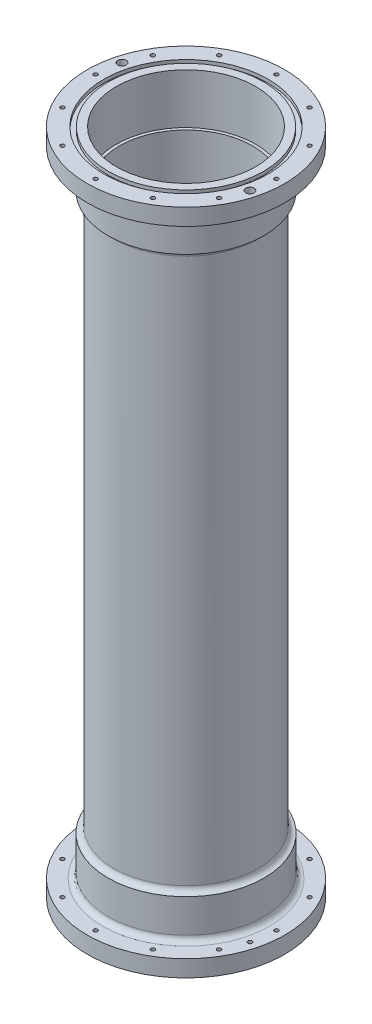
SolidWorks part; units mm, degrees
material "7075-T6 (SN)"
ref_plane "Front Plane" through (0, 0, 0) normal (0, 0, 1) x (1, 0, 0)
ref_plane "Top Plane" through (0, 0, 0) normal (0, 1, 0) x (1, 0, 0)
ref_plane "Right Plane" through (0, 0, 0) normal (1, 0, 0) x (0, 0, -1)
sketch "Sketch2" plane through (0, 0, 0) normal (0, 1, 0) x (1, 0, 0)
  circle A0 centre (0, 0) radius 38.1
  circle A1 centre (0, 0) radius 41.275
  dimension "D1" = 82.55
  dimension "D2" = 76.2
extrude "Base Cylinder" add sketch "Sketch2" along normal blind 381
sketch "Sketch3" plane through (0, 0, 0) normal (0, -1, 0) x (1, 0, 0)
  circle A0 centre (0, 0) radius 38.1
  circle A1 centre (0, 0) radius 56.3562
  dimension "D1" = 112.7125
extrude "Aft Flange" add sketch "Sketch3" against normal blind 9.525
sketch "Sketch34" plane through (0, 0, 0) normal (0, -1, 0) x (1, 0, 0)
  circle A0 centre (0, 0) radius 39.75
  dimension "D1" = 79.5
extrude "TemperatureInsert" cut sketch "Sketch34" against normal blind 28.575
sketch "Sketch6" plane through (0, 0, 0) normal (0, -1, 0) x (1, 0, 0)
  circle A0 centre (0, 0) radius 46.9011
  circle A1 centre (0, 0) radius 44.2849
  dimension "D1" = 93.8022
  dimension "D2" = 88.5698
extrude "Aft O-Ring" cut sketch "Sketch6" against normal blind 1.9812
sketch "Sketch33" plane through (0, 9.525, 0) normal (0, 1, 0) x (1, 0, 0)
  circle A0 centre (0, 0) radius 41.275
  circle A1 centre (0, 0) radius 44.45
  dimension "D1" = 82.55
  dimension "D2" = 88.9
extrude "CriticalBoss" add sketch "Sketch33" along normal blind 22.225
fillet "Fillet1" radius 3.175 2 edges at (0, 9.525, -44.45) (0, 31.75, 41.275)
sketch "Sketch For Bolt Holes" plane through (0, 0, 0) normal (0, -1, 0) x (1, 0, 0)
  circle A0 centre (-51.6255, 0) radius 1.5875
  circle A1 centre (-44.709, 25.8128) radius 1.5875
  circle A2 centre (-25.8128, 44.709) radius 1.5875
  circle A3 centre (0, 51.6255) radius 1.5875
  circle A4 centre (25.8127, 44.709) radius 1.5875
  circle A5 centre (44.709, 25.8128) radius 1.5875
  circle A6 centre (51.6255, 0) radius 1.5875
  circle A7 centre (44.709, -25.8127) radius 1.5875
  circle A8 centre (25.8128, -44.709) radius 1.5875
  circle A9 centre (0, -51.6255) radius 1.5875
  circle A10 centre (-25.8127, -44.709) radius 1.5875
  circle A11 centre (-44.709, -25.8128) radius 1.5875
  point P36 (0, 0)
  dimension "D2" = 3.175
  dimension "D1" = 51.6255
  dimension "D3" = 12
hole_wizard "Bolt Circle" positions "Sketch8" profile "Sketch9" hole size "#4-40" standard "ANSI Inch" end condition up to next
sketch "Sketch8" plane through (0, 0, 0) normal (0, -1, 0) x (-1, 0, 0)
  point P0 (-25.8127, -44.709)
  point P3 (-44.709, -25.8128)
  point P6 (-51.6255, 0)
  point P9 (-44.709, 25.8127)
  point P12 (-25.8128, 44.709)
  point P15 (0, 51.6255)
  point P18 (25.8127, 44.709)
  point P21 (44.709, 25.8128)
  point P24 (51.6255, 0)
  point P27 (44.709, -25.8128)
  point P30 (25.8128, -44.709)
  point P33 (0, -51.6255)
  point P36 (-25.8127, -44.709)
  point P38 (-44.709, -25.8128)
  point P40 (-51.6255, 0)
sketch "Sketch9" plane through (25.8127, 0, 44.709) normal (1, 0, 0) x (0, 0, -1)
  line L0 (0, 0) -> (0, 381)
  line L1 (0, 381) -> (1.1303, 381)
  line L2 (1.1303, 381) -> (1.1303, 0)
  line L5 (1.1303, 0) -> (0, 0)
  line L11 (0, -6.35) -> (0, 107.95) construction
  dimension "Thru Hole Dia." = 2.2606
  dimension "Thru Hole Depth" = 381
sketch "Dowel Hole Sketch" plane through (0, 0, 0) normal (0, -1, 0) x (1, 0, 0)
  line L0 (0, 0) -> (-51.6255, 0) construction
  line L1 (0, 0) -> (-49.8664, -13.3617) construction
  line L2 (0, 0) -> (0, -51.6255) construction
  line L3 (0, 0) -> (49.8664, 13.3617) construction
  circle A0 centre (0, 0) radius 51.6255
  circle A1 centre (-49.8664, -13.3617) radius 4.6172
  circle A2 centre (49.8664, 13.3617) radius 3.4532
  dimension "D1" = 15
hole_wizard "Hole1" positions "Sketch14" profile "Sketch12" legacy end condition up to next
sketch "Sketch14" plane through (0, 0, 0) normal (0, -1, 0) x (-1, 0, 0)
  point P0 (49.8664, 13.3617)
  point P3 (-49.8664, -13.3617)
sketch "Sketch12" plane through (-49.8664, 0, -13.3617) normal (1, 0, 0) x (0, 0, -1)
  line L0 (0, 0) -> (0, 381)
  line L1 (0, 381) -> (1.1906, 381)
  line L2 (1.1906, 381) -> (1.1906, 4.7625)
  line L3 (1.1906, 4.7625) -> (2.3813, 4.7625)
  line L4 (2.3813, 4.7625) -> (2.3813, 0)
  line L5 (2.3813, 0) -> (0, 0)
  line L6 (0, 110) -> (0, -10) construction
  dimension "Diameter" = 2.3813
  dimension "Depth" = 381
  dimension "C-Bore Diameter" = 4.7625
  dimension "C-Bore Depth" = 4.7625
ref_plane "Hoop Mid-Plane" through (0, 190.5, 0) normal (0, 1, 0) x (1, 0, 0)
ref_plane "PressureTapHolePlane" through (0, 0, 44.45) normal (0, 0, 1) x (1, 0, 0)
ref_plane "TemperatureTapPlane" through (0, 0, -44.45) normal (0, 0, 1) x (1, 0, 0)
sketch "ThermoHole" plane through (0, 0, -44.45) normal (0, 0, 1) x (1, 0, 0)
  line L0 (-56.3562, 0) -> (56.3562, 0) construction
  circle A0 centre (0, 19.05) radius 3.175
  dimension "D1" = 19.05
  dimension "D2" = 6.35
sketch "Sketch35" plane through (0, 0, 44.45) normal (0, 0, 1) x (1, 0, 0)
  line L0 (-56.3562, 0) -> (56.3562, 0) construction
  circle A0 centre (0, 19.05) radius 1.5875
  dimension "D1" = 19.05
  dimension "D2" = 3.175
extrude "Pressure Tap Aft Big" [suppressed] cut sketch "Sketch35" against normal blind 2.3813
sketch "Sketch41" [suppressed] plane through (0, 0, 42.0687) normal (0, 0, 1) x (1, 0, 0)
  circle A0 centre (0, 19.05) radius 0.1984
extrude "Pressure Tap Aft Small" [suppressed] cut sketch "Sketch41" against normal up to next
hole_wizard "1/8 NPT Tapped ThermocoupleHole" [suppressed] positions "Sketch43" profile "Sketch44" size "1/8" standard "ANSI Inch"
sketch "Sketch43" plane through (0, 0, -44.45) normal (0, 0, 1) x (1, 0, 0)
  point P0 (0, 19.05)
sketch "Sketch44" plane through (0, 19.05, -44.45) normal (1, 0, 0) x (0, 1, 0)
  line L0 (0, 0) -> (0, 14.2175)
  line L1 (4.2164, 11.684) -> (0, 14.2175)
  line L2 (-4.2164, 11.684) -> (0, 14.2175) construction
  line L3 (4.2164, 11.684) -> (4.2164, 6.858)
  line L4 (4.2164, 6.858) -> (4.9362, 6.858)
  line L5 (4.9362, 6.858) -> (5.1415, 0)
  line L6 (-4.9362, 6.858) -> (-5.1415, 0) construction
  line L7 (5.1415, 0) -> (0, 0)
  line L8 (0, -6.35) -> (0, 107.95) construction
  line L11 (-4.2164, 6.858) -> (-4.9362, 6.858) construction
  dimension "Tap Drill Dia." = 8.4328
  dimension "Tap Drill Depth" = 11.684
  dimension "Thread Dia." = 10.283
  dimension "Thread Angle" = 3.43
  dimension "Thread Depth" = 6.858
  dimension "Drill Angle" = 118
mirror "Mirror1" about plane through (0, 190.5, 0) normal (0, 1, 0) of "Hole1", "Bolt Circle", "Fillet1", "CriticalBoss", "Aft O-Ring", "TemperatureInsert", "Aft Flange"
